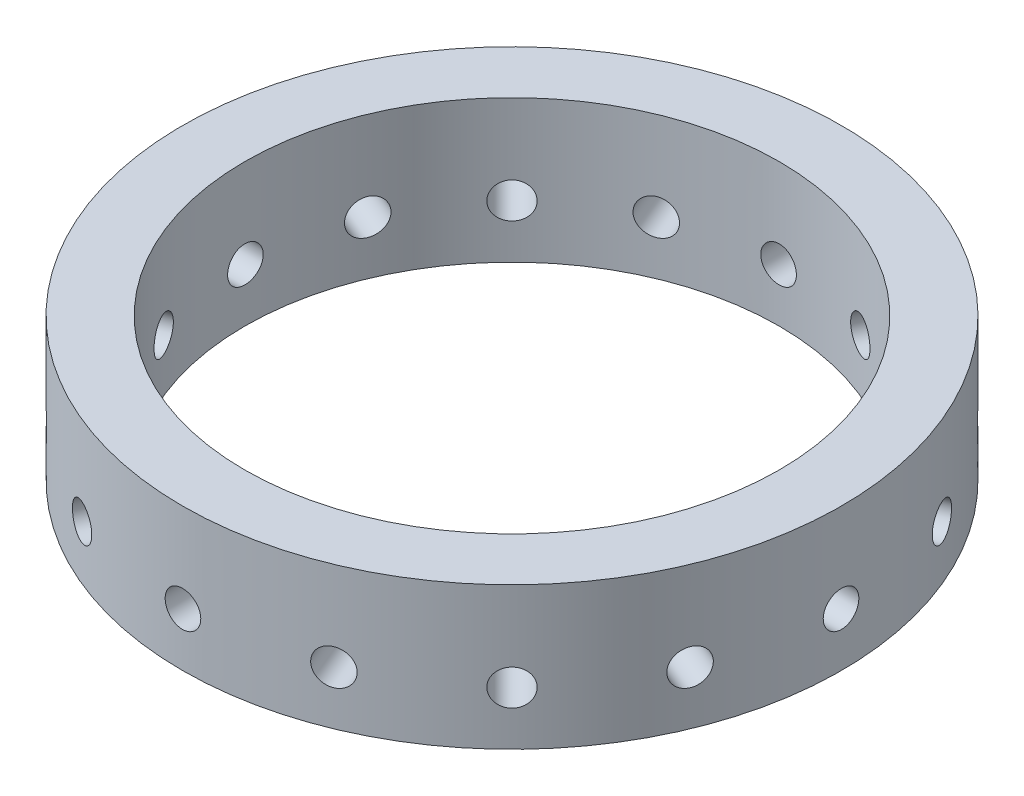
SolidWorks part; units mm, degrees
material "6061-T6 (SS)"
ref_plane "Front Plane" through (0, 0, 0) normal (0, 0, 1) x (1, 0, 0)
ref_plane "Top Plane" through (0, 0, 0) normal (0, 1, 0) x (1, 0, 0)
ref_plane "Right Plane" through (0, 0, 0) normal (1, 0, 0) x (0, 0, -1)
sketch "Sketch1" plane through (0, 0, 0) normal (0, 1, 0) x (1, 0, 0)
  circle A0 centre (0, 0) radius 58.7375
  circle A1 centre (0, 0) radius 47.625
extrude "Boss-Extrude1" add sketch "Sketch1" along normal blind 25.4
ref_plane "Plane1" through (0, 0, -58.7375) normal (0, 0, -1) x (-1, 0, 0)
sketch "Sketch2" plane through (0, 0, -58.7375) normal (0, 0, -1) x (-1, 0, 0)
  line L0 (0, 0) -> (0, 9.525)
  point P4 (0, 9.525)
hole_wizard "1/4 (0.25) Diameter Hole1" positions "Sketch3" profile "Sketch4" hole size "1/4" standard "ANSI Inch" end condition through all
sketch "Sketch3" plane through (0, 0, -58.7375) normal (0, 0, -1) x (-1, 0, 0)
  point P0 (0, 9.525)
sketch "Sketch4" plane through (0, 9.525, -58.7375) normal (1, 0, 0) x (0, 1, 0)
  line L0 (0, 0) -> (0, 117.475)
  line L1 (0, 117.475) -> (3.175, 117.475)
  line L2 (3.175, 117.475) -> (3.175, 0)
  line L5 (3.175, 0) -> (0, 0)
  line L11 (0, -6.35) -> (0, 107.95) construction
  dimension "Thru Hole Dia." = 6.35
  dimension "Thru Hole Depth" = 117.475
sketch "Sketch5" plane through (0, 0, 0) normal (0, 0, 1) x (1, 0, 0)
  line L0 (0, 0) -> (0, 24.4952)
pattern_circular "CirPattern1" count 16 over 360 about axis through (0, 0, 0) along (0, 1, 0) of "1/4 (0.25) Diameter Hole1" reverse direction yes
ref_plane "Plane2" through (0, 9.525, 0) normal (0, 1, 0) x (1, 0, 0)
